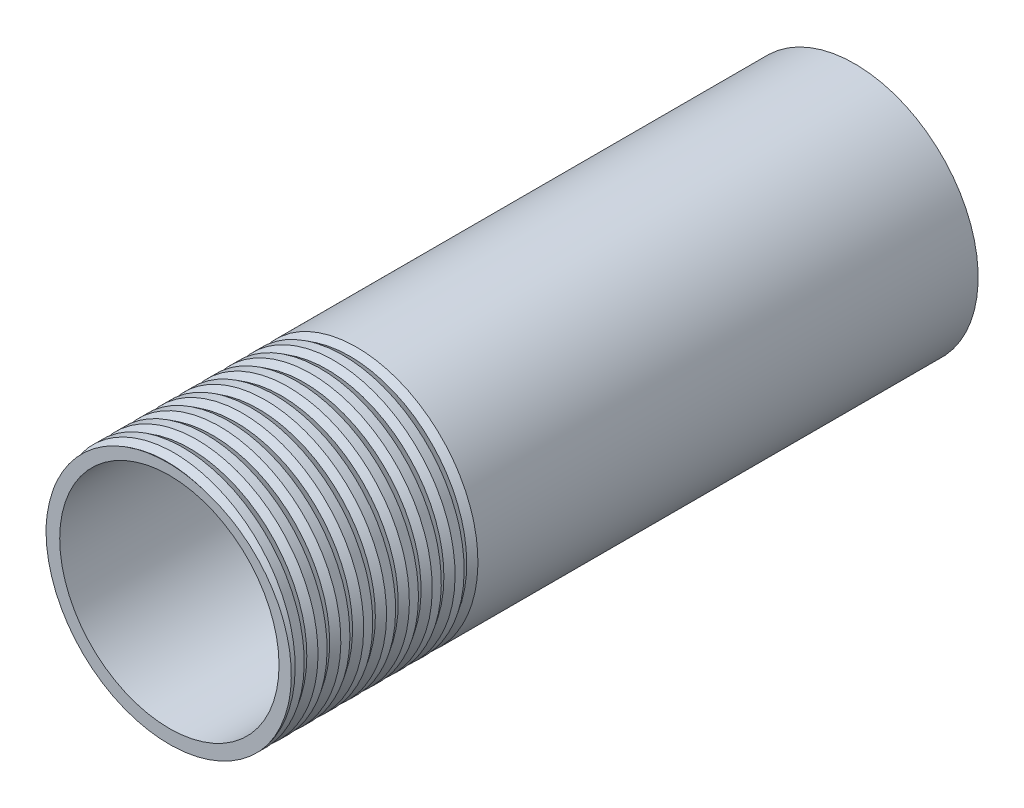
SolidWorks part; units mm, degrees
ref_plane "Front Plane" through (0, 0, 0) normal (0, 0, 1) x (1, 0, 0)
ref_plane "Top Plane" through (0, 0, 0) normal (0, 1, 0) x (1, 0, 0)
ref_plane "Right Plane" through (0, 0, 0) normal (1, 0, 0) x (0, 0, -1)
sketch "Sketch1" plane through (0, 0, 0) normal (0, 0, 1) x (1, 0, 0)
  circle A0 centre (0, 0) radius 13.5
  circle A1 centre (0, 0) radius 12
  dimension "D1" = 1.5
  dimension "D2" = 27
extrude "Boss-Extrude1" add sketch "Sketch1" along normal blind 125
sketch "Sketch3" plane through (0, 0, 125) normal (0, 0, 1) x (1, 0, 0)
  circle A2 centre (0, 0) radius 13.5 construction
  circle A3 centre (0, 0) radius 13.5
curve "Helix/Spiral2" pitch 2.5 height 20 radius 13.5 left hand yes centre (0, 0, 125) axis (0, 0, -1) start towards (-1, 0, 0)
sketch "Sketch6" plane through (0, 0, 0) normal (0, 1, 0) x (1, 0, 0)
  line L3 (-13.5, -125) -> (-13.5, -123.4929)
  line L4 (-13.5, 0) -> (-13.5, -125) construction
  line L5 (-13.5, -123.4929) -> (-13.0298, -124.2465)
  line L6 (-13.5, -125) -> (-13.0298, -124.2465)
sweep "Cut-Sweep5" cut profiles "Sketch6" path "Helix/Spiral2" align with end faces yes
sketch "Sketch7" plane through (0, 0, 0) normal (0, 0, -1) x (-1, 0, 0)
  circle A0 centre (0, 0) radius 13.5 construction
  circle A1 centre (0, 0) radius 13.5
extrude "Cut-Extrude1" cut sketch "Sketch7" against normal blind 50
